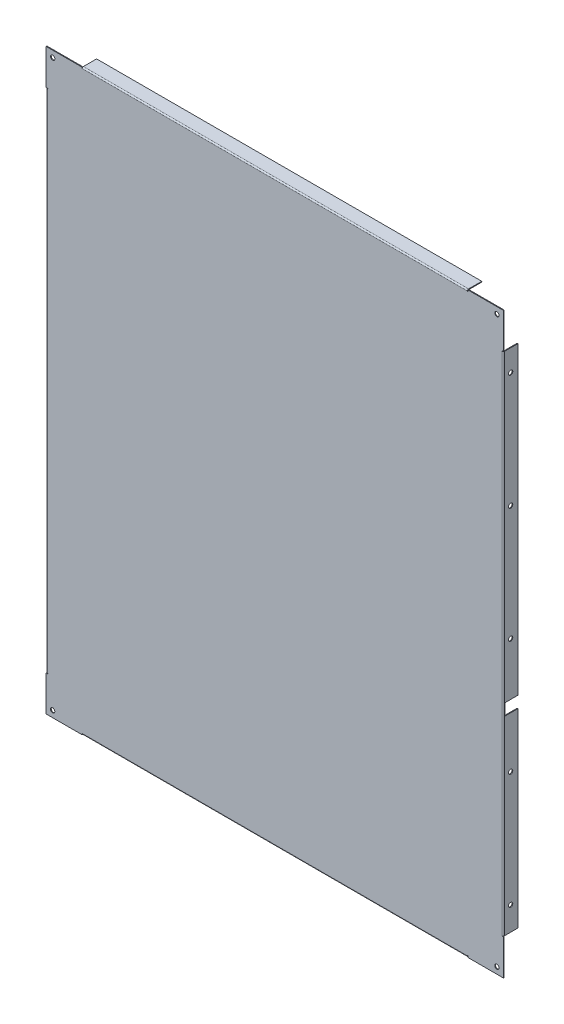
SolidWorks part; units mm, degrees
note: The reader was unsure of these and kept them because the rebuilt part matched: flange length of "边线-法兰1", "边线-法兰2", "边线-法兰3".
ref_plane "前视基准面" through (0, 0, 0) normal (0, 0, 1) x (1, 0, 0)
ref_plane "上视基准面" through (0, 0, 0) normal (0, 1, 0) x (1, 0, 0)
ref_plane "右视基准面" through (0, 0, 0) normal (1, 0, 0) x (0, 0, -1)
sketch "草图1" plane through (0, 0, 0) normal (0, 0, 1) x (1, 0, 0)
  line L1 (-317.5, 401.5) -> (317.5, 401.5)
  line L2 (-317.5, 401.5) -> (-317.5, -401.5)
  line L3 (-317.5, -401.5) -> (317.5, -401.5)
  line L4 (317.5, 401.5) -> (317.5, -401.5)
  line L5 (-317.5, 401.5) -> (317.5, -401.5) construction
  line L6 (-317.5, -401.5) -> (317.5, 401.5) construction
  point P0 (0, 0)
  dimension "D1" = 635
  dimension "D2" = 803
sheet metal parameters "钣金1" thickness 1 parameters "D1"=0.7366
base flange "基体-法兰1" sketch "草图1" thickness 1 reverse thickness direction no parameters "D1"=0.7366
edge flange "边线-法兰1" sketch "草图7" flange angle 90 flange length 19 flange position material inside bend radius 0.7366 thickness 1 relief rectangular parameters "D6"=10
sketch "草图7" plane through (0, 401.5, -1) normal (0, 1, 0) x (1, 0, 0)
  line L0 (317.5, 0) -> (-317.5, 0) construction
  line L1 (267.5, 0) -> (-267.5, 0)
  line L2 (-267.5, 0) -> (-267.5, 19)
  line L3 (-267.5, 19) -> (267.5, 19)
  line L4 (267.5, 19) -> (267.5, 0)
  line L5 (317.5, -1) -> (-317.5, -1) construction
  line L6 (-317.5, 0) -> (-317.5, -1) construction
  line L7 (317.5, 0) -> (317.5, -1) construction
  dimension "D1" = 20
  dimension "D2" = 50
  dimension "D3" = 50
bend "边线折弯1" bend radius 0.7366 bend angle 90 parameters "D5"=1
edge flange "边线-法兰2" sketch "草图10" flange angle 90 flange length 19 flange position material inside bend radius 0.7366 thickness 1 relief rectangular parameters "D6"=10
sketch "草图10" plane through (0, -401.5, -1) normal (0, -1, 0) x (-1, 0, 0)
  line L2 (-267.5, 0) -> (-267.5, 19)
  line L3 (-267.5, 19) -> (267.5, 19)
  line L4 (267.5, 19) -> (267.5, 0)
  line L5 (317.5, 0) -> (-317.5, 0) construction
  line L6 (267.5, 0) -> (-267.5, 0)
  line L7 (317.5, 0) -> (317.5, -1) construction
  line L8 (317.5, -1) -> (-317.5, -1) construction
  line L9 (-317.5, 0) -> (-317.5, -1) construction
  point P6 (317.5, -0.5)
  dimension "D1" = 50
  dimension "D2" = 20
  dimension "D3" = 50
bend "边线折弯2" bend radius 0.7366 bend angle 90 parameters "D5"=2
edge flange "边线-法兰3" sketch "草图13" flange angle 90 flange length 20 flange position material inside bend radius 0.7366 thickness 1 relief rectangular parameters "D6"=10
sketch "草图13" plane through (317.5, 0, -1) normal (1, 0, 0) x (0, -1, 0)
  line L0 (401.5, 0) -> (-401.5, 0) construction
  line L1 (351.5, 0) -> (-351.5, 0)
  line L2 (-351.5, 0) -> (-351.5, 19)
  line L3 (-351.5, 19) -> (71.5, 19)
  line L4 (351.5, 19) -> (351.5, 0)
  line L5 (401.5, 0) -> (401.5, -1) construction
  line L6 (-401.5, 0) -> (-401.5, -1) construction
  line L7 (401.5, -1) -> (-401.5, -1) construction
  line L8 (87.5, 19) -> (351.5, 19)
  line L10 (87.5, 19) -> (87.5, 1)
  line L11 (87.5, 1) -> (71.5, 1)
  line L12 (71.5, 19) -> (71.5, 1)
  dimension "D1" = 50
  dimension "D2" = 50
  dimension "D3" = 20
  dimension "D4" = 16
  dimension "D5" = 264
  dimension "D6" = 2
bend "边线折弯3" bend radius 0.7366 bend angle 90 parameters "D5"=3
mirror "镜向1" about plane through (0, 0, 0) normal (1, 0, 0) of "边线-法兰3"
bend "镜向折弯1" bend radius 0.7366 bend angle 90 parameters "D5"=4
sketch "草图15" plane through (317.5, 0, 0) normal (1, 0, 0) x (0, 0, -1)
  line L0 (1.7366, 401.5) -> (20, 401.5) construction
  line L2 (20, -71.5) -> (20, 351.5) construction
  circle A0 centre (10, 321.5) radius 3
  circle A1 centre (10, 161.5) radius 3
  circle A2 centre (10, 1.5) radius 3
  circle A3 centre (10, -158.5) radius 3
  circle A4 centre (10, -318.5) radius 3
  dimension "D6" = 6
  dimension "D1" = 160
  dimension "D2" = 80
  dimension "D3" = 160
  dimension "D4" = 160
  dimension "D5" = 160
  dimension "D7" = 10
extrude "切除-拉伸2" cut sketch "草图15" against normal through all normal cut yes
sketch "草图16" plane through (0, 0, 0) normal (0, 0, 1) x (1, 0, 0)
  line L1 (308.5, 392.5) -> (-308.5, 392.5) construction
  line L2 (308.5, 392.5) -> (308.5, -392.5) construction
  line L3 (308.5, -392.5) -> (-308.5, -392.5) construction
  line L4 (-308.5, 392.5) -> (-308.5, -392.5) construction
  line L5 (308.5, 392.5) -> (-308.5, -392.5) construction
  line L6 (308.5, -392.5) -> (-308.5, 392.5) construction
  circle A0 centre (308.5, 392.5) radius 3
  circle A1 centre (308.5, -392.5) radius 3
  circle A2 centre (-308.5, 392.5) radius 3
  circle A3 centre (-308.5, -392.5) radius 3
  point P0 (0, 0)
  dimension "D3" = 6
  dimension "D1" = 617
  dimension "D2" = 785
extrude "切除-拉伸3" cut sketch "草图16" against normal through all normal cut yes
flat pattern "平板型式1" [suppressed]
sketch "折弯-线1" plane through (0, 0, 0) normal (0, 1, 0) x (-1, 0, 0)
bend of the flat pattern "展开-<边线折弯1>1"
bend of the flat pattern "展开-<边线折弯2>1"
bend of the flat pattern "展开-<边线折弯3>1"
bend of the flat pattern "展开-<镜向折弯1>1"
